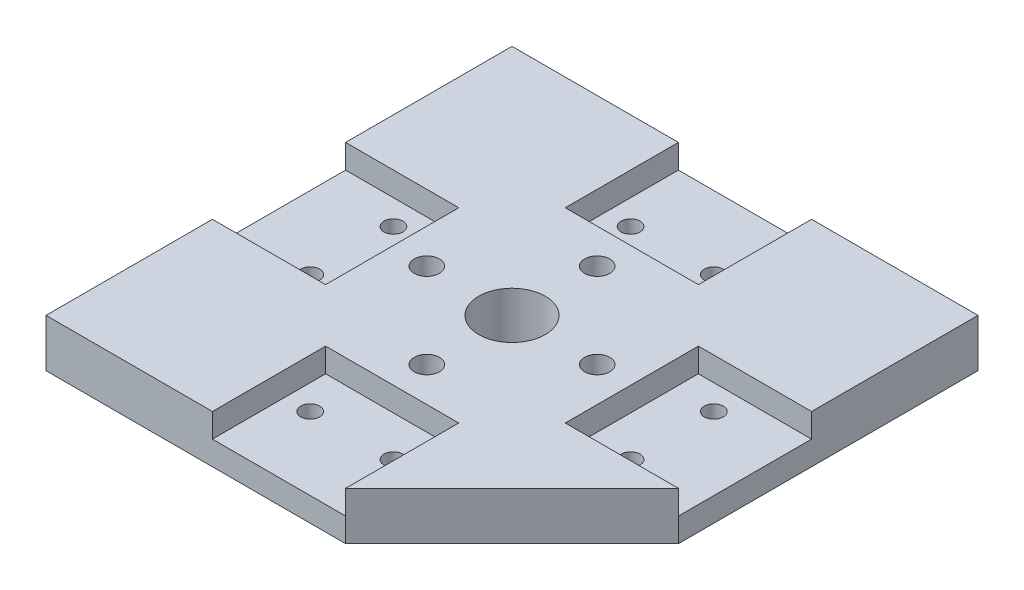
SolidWorks part; units mm, degrees
material "6061 Alloy"
ref_plane "Front Plane" through (0, 0, 0) normal (0, 0, 1) x (1, 0, 0)
ref_plane "Top Plane" through (0, 0, 0) normal (0, 1, 0) x (1, 0, 0)
ref_plane "Right Plane" through (0, 0, 0) normal (1, 0, 0) x (0, 0, -1)
sketch "Sketch1" plane through (0, 0, 0) normal (0, 1, 0) x (1, 0, 0)
  line L1 (0, 0) -> (88.9, 0)
  line L2 (0, 0) -> (0, 88.9)
  line L3 (0, 88.9) -> (88.9, 88.9)
  line L4 (88.9, 0) -> (88.9, 88.9)
  dimension "D1" = 88.9
  dimension "D2" = 88.9
extrude "Boss-Extrude1" add sketch "Sketch1" along normal blind 9.144
sketch "Sketch2" plane through (0, 9.144, 0) normal (0, 1, 0) x (1, 0, 0)
  line L0 (88.9, 88.9) -> (0, 88.9) construction
  line L1 (31.75, 88.9) -> (57.15, 88.9)
  line L2 (31.75, 88.9) -> (31.75, 67.31)
  line L3 (31.75, 67.31) -> (57.15, 67.31)
  line L4 (57.15, 88.9) -> (57.15, 67.31)
  line L5 (0, 88.9) -> (0, 0) construction
  line L6 (0, 57.15) -> (21.59, 57.15)
  line L7 (0, 57.15) -> (0, 31.75)
  line L8 (0, 31.75) -> (21.59, 31.75)
  line L9 (21.59, 57.15) -> (21.59, 31.75)
  line L10 (0, 0) -> (88.9, 0) construction
  line L11 (31.75, 0) -> (57.15, 0)
  line L12 (31.75, 0) -> (31.75, 21.59)
  line L13 (31.75, 21.59) -> (57.15, 21.59)
  line L14 (57.15, 0) -> (57.15, 21.59)
  line L15 (88.9, 0) -> (88.9, 88.9) construction
  line L16 (88.9, 57.15) -> (67.31, 57.15)
  line L17 (88.9, 57.15) -> (88.9, 31.75)
  line L18 (88.9, 31.75) -> (67.31, 31.75)
  line L19 (67.31, 57.15) -> (67.31, 31.75)
  dimension "D1" = 31.75
  dimension "D2" = 25.4
  dimension "D3" = 25.4
  dimension "D4" = 31.75
  dimension "D5" = 25.4
  dimension "D6" = 31.75
  dimension "D7" = 25.4
  dimension "D8" = 31.75
  dimension "D9" = 21.59
  dimension "D10" = 21.59
  dimension "D11" = 21.59
  dimension "D12" = 21.59
extrude "Cut-Extrude1" cut sketch "Sketch2" against normal blind 4.572
sketch "Sketch3" plane through (0, 9.144, 0) normal (0, 1, 0) x (1, 0, 0)
  line L0 (31.75, 88.9) -> (0, 88.9) construction
  line L1 (20.6375, 68.2625) -> (68.2625, 68.2625)
  line L2 (20.6375, 68.2625) -> (20.6375, 20.6375)
  line L3 (20.6375, 20.6375) -> (68.2625, 20.6375)
  line L4 (68.2625, 68.2625) -> (68.2625, 20.6375)
  line L5 (0, 31.75) -> (0, 0) construction
  line L6 (88.9, 31.75) -> (88.9, 57.15) construction
  line L7 (57.15, 88.9) -> (31.75, 88.9) construction
  line L8 (0, 57.15) -> (0, 31.75) construction
  line L9 (31.75, 0) -> (57.15, 0) construction
  circle A0 centre (28.194, 44.45) radius 2.4
  circle A1 centre (44.45, 60.706) radius 2.4
  circle A2 centre (60.706, 44.45) radius 2.4
  circle A3 centre (44.45, 28.194) radius 2.4
  dimension "D5" = 4.8
  dimension "D6" = 4.8
  dimension "D7" = 4.8
  dimension "D8" = 4.8
  dimension "D1" = 47.625
  dimension "D2" = 47.625
  dimension "D3" = 20.6375
  dimension "D4" = 20.6375
  dimension "D9" = 28.194
  dimension "D10" = 28.194
  dimension "D11" = 28.194
  dimension "D12" = 28.194
  dimension "D13" = 23.8125
  dimension "D14" = 23.8125
  dimension "D15" = 23.8125
  dimension "D16" = 23.8125
extrude "Cut-Extrude2" cut sketch "Sketch3" against normal through all contours A2 | A1 | A0 | A3
sketch "Sketch4" plane through (0, 4.572, 0) normal (0, 1, 0) x (1, 0, 0)
  line L0 (0, 57.15) -> (0, 31.75) construction
  line L1 (57.15, 88.9) -> (31.75, 88.9) construction
  line L2 (88.9, 31.75) -> (88.9, 57.15) construction
  line L3 (31.75, 0) -> (57.15, 0) construction
  line L4 (0, 31.75) -> (21.59, 31.75) construction
  line L5 (31.75, 21.59) -> (31.75, 0) construction
  line L6 (67.31, 31.75) -> (88.9, 31.75) construction
  line L7 (57.15, 67.31) -> (57.15, 88.9) construction
  circle A0 centre (75.0062, 52.3875) radius 1.8034
  circle A1 centre (75.0062, 36.5125) radius 1.8034
  circle A2 centre (52.3875, 75.0062) radius 1.8034
  circle A3 centre (36.5125, 75.0062) radius 1.8034
  circle A4 centre (13.8938, 52.3875) radius 1.8034
  circle A5 centre (13.8938, 36.5125) radius 1.8034
  circle A6 centre (36.5125, 13.8938) radius 1.8034
  circle A7 centre (52.3875, 13.8938) radius 1.8034
  dimension "D1" = 3.6068
  dimension "D2" = 3.6068
  dimension "D3" = 3.6068
  dimension "D4" = 3.6068
  dimension "D5" = 3.6068
  dimension "D6" = 3.6068
  dimension "D7" = 3.6068
  dimension "D8" = 3.6068
  dimension "D9" = 13.8938
  dimension "D10" = 13.8938
  dimension "D11" = 13.8938
  dimension "D12" = 13.8938
  dimension "D13" = 13.8938
  dimension "D14" = 13.8938
  dimension "D15" = 13.8938
  dimension "D16" = 13.8938
  dimension "D17" = 15.875
  dimension "D18" = 4.7625
  dimension "D19" = 4.7625
  dimension "D20" = 15.875
  dimension "D21" = 4.7625
  dimension "D22" = 15.875
  dimension "D23" = 4.7625
  dimension "D24" = 15.875
extrude "Cut-Extrude3" cut sketch "Sketch4" against normal through all
sketch "Sketch5" plane through (0, 9.144, 0) normal (0, 1, 0) x (1, 0, 0)
  line L0 (88.9, 88.9) -> (57.15, 88.9) construction
  line L1 (88.9, 31.75) -> (88.9, 57.15) construction
  circle A0 centre (44.45, 44.45) radius 6.35
  dimension "D1" = 12.7
  dimension "D2" = 44.45
  dimension "D3" = 44.45
extrude "Cut-Extrude4" cut sketch "Sketch5" against normal through all
sketch "Sketch6" plane through (0, 9.144, 0) normal (0, 1, 0) x (1, 0, 0)
  line L0 (88.9, 31.75) -> (57.15, 0)
  line L1 (57.15, 0) -> (88.9, 0)
  line L2 (88.9, 0) -> (88.9, 31.75)
extrude "Cut-Extrude5" cut sketch "Sketch6" against normal through all
equation "\"hinge_hole\"= 0.142in"
equation "\"D1@Sketch4\"=\"hinge_hole\""
equation "\"D2@Sketch4\"=\"hinge_hole\""
equation "\"D3@Sketch4\"=\"hinge_hole\""
equation "\"D4@Sketch4\"=\"hinge_hole\""
equation "\"D5@Sketch4\"=\"hinge_hole\""
equation "\"D6@Sketch4\"=\"hinge_hole\""
equation "\"D7@Sketch4\"=\"hinge_hole\""
equation "\"D8@Sketch4\"=\"hinge_hole\""
equation "\"hinge_hole_dist\"= 0.297 + 0.25"
equation "\"D9@Sketch4\"=\"hinge_hole_dist\""
equation "\"D10@Sketch4\"=\"hinge_hole_dist\""
equation "\"D11@Sketch4\"=\"hinge_hole_dist\""
equation "\"D12@Sketch4\"=\"hinge_hole_dist\""
equation "\"D13@Sketch4\"=\"hinge_hole_dist\""
equation "\"D14@Sketch4\"=\"hinge_hole_dist\""
equation "\"D15@Sketch4\"=\"hinge_hole_dist\""
equation "\"D16@Sketch4\"=\"hinge_hole_dist\""
equation "\"hinge_hole_sep\"= 0.625"
equation "\"hinge_hole_from_wall\"= ( 1 - \"hinge_hole_sep\" ) / 2"
equation "\"D17@Sketch4\"=\"hinge_hole_sep\""
equation "\"D18@Sketch4\"=\"hinge_hole_from_wall\""
equation "\"D19@Sketch4\"=\"hinge_hole_from_wall\""
equation "\"D20@Sketch4\"=\"hinge_hole_sep\""
equation "\"D21@Sketch4\"=\"hinge_hole_from_wall\""
equation "\"D22@Sketch4\"=\"hinge_hole_sep\""
equation "\"D23@Sketch4\"=\"hinge_hole_from_wall\""
equation "\"D24@Sketch4\"=\"hinge_hole_sep\""
equation "\"D9@Sketch2\"=\"hinge_hole_dist\" + (0.6-0.297)"
equation "\"D12@Sketch2\"=\"hinge_hole_dist\" + (0.6-0.297)"
equation "\"D11@Sketch2\"=\"hinge_hole_dist\" + (0.6-0.297)"
equation "\"D10@Sketch2\"=\"hinge_hole_dist\" + (0.6-0.297)"
